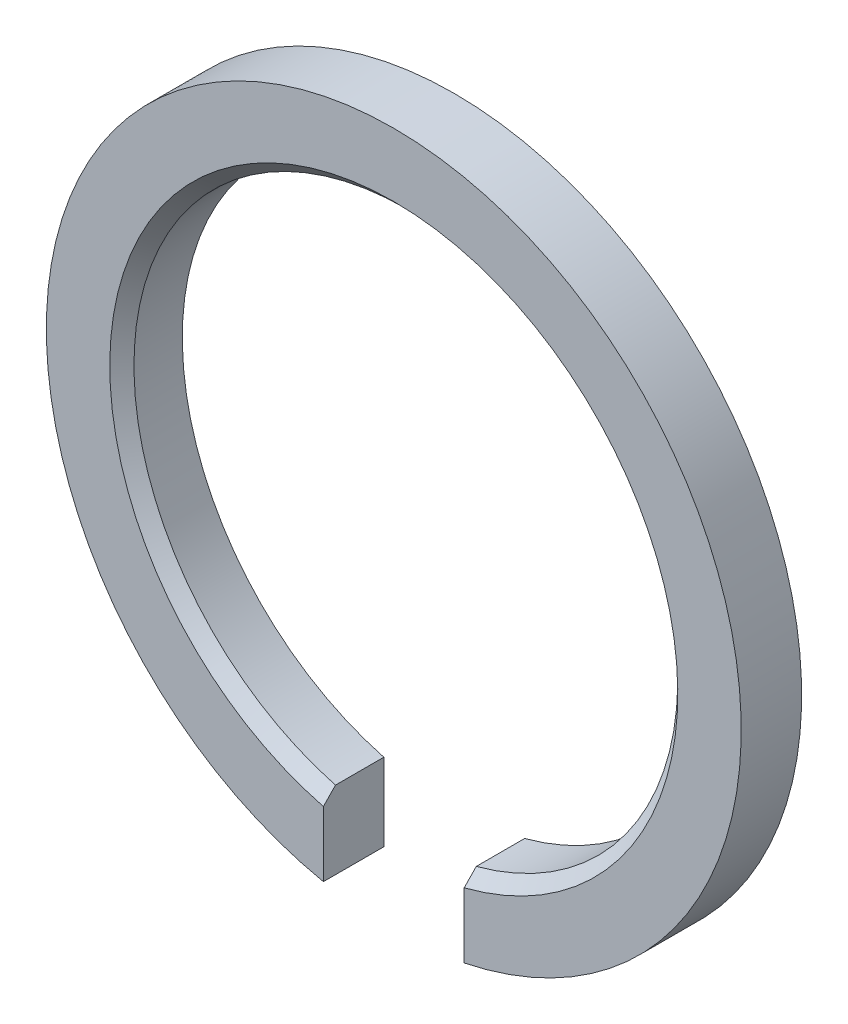
SolidWorks part; units mm, degrees
material "ABS"
ref_plane "Front Plane" through (0, 0, 0) normal (1, 0, 0) x (0, 1, 0)
ref_plane "Top Plane" through (0, 0, 0) normal (0, 0, 1) x (0, 1, 0)
ref_plane "Right Plane" through (0, 0, 0) normal (0, 1, 0) x (-1, 0, 0)
sketch "Sketch1" plane through (0, 0, 0) normal (0, 0, 1) x (0, 1, 0)
  circle A0 centre (0, 0) radius 57.5
  circle A1 centre (0, 0) radius 45
  dimension "D1" = 90
extrude "Boss-Extrude1" add sketch "Sketch1" along normal blind 10
sketch "Sketch2" plane through (0, 0, 0) normal (0, 0, -1) x (1, 0, 0)
  line L0 (0, 0) -> (0, 57.8453) construction
  line L1 (11.6505, 56.6599) -> (11.6505, 43.4657)
  line L3 (-11.6505, 43.4657) -> (-11.6505, 56.6599)
  circle A0 centre (0, 0) radius 57.8453 construction
  circle A5 centre (0, 0) radius 45 construction
  arc A10 (11.6505, 56.6599) -> (-11.6505, 56.6599) centre (0, 0) ccw
  spline S0 degree 2 poles (11.6505, 43.4657) (-0.6792, 46.4064) (-11.6505, 43.4657) knots 0 0 0 0.575547 0.575547 0.575547
  point P5 (0, 57.8453)
extrude "Cut-Extrude2" cut sketch "Sketch2" against normal blind 10
fillet "Chamfer1" radius 2 1 edges at (0, 45, 10) type face fillet profile chamfer first side face at (0, 0.6817, 10) second side face at (0, 0.7672, 5)
